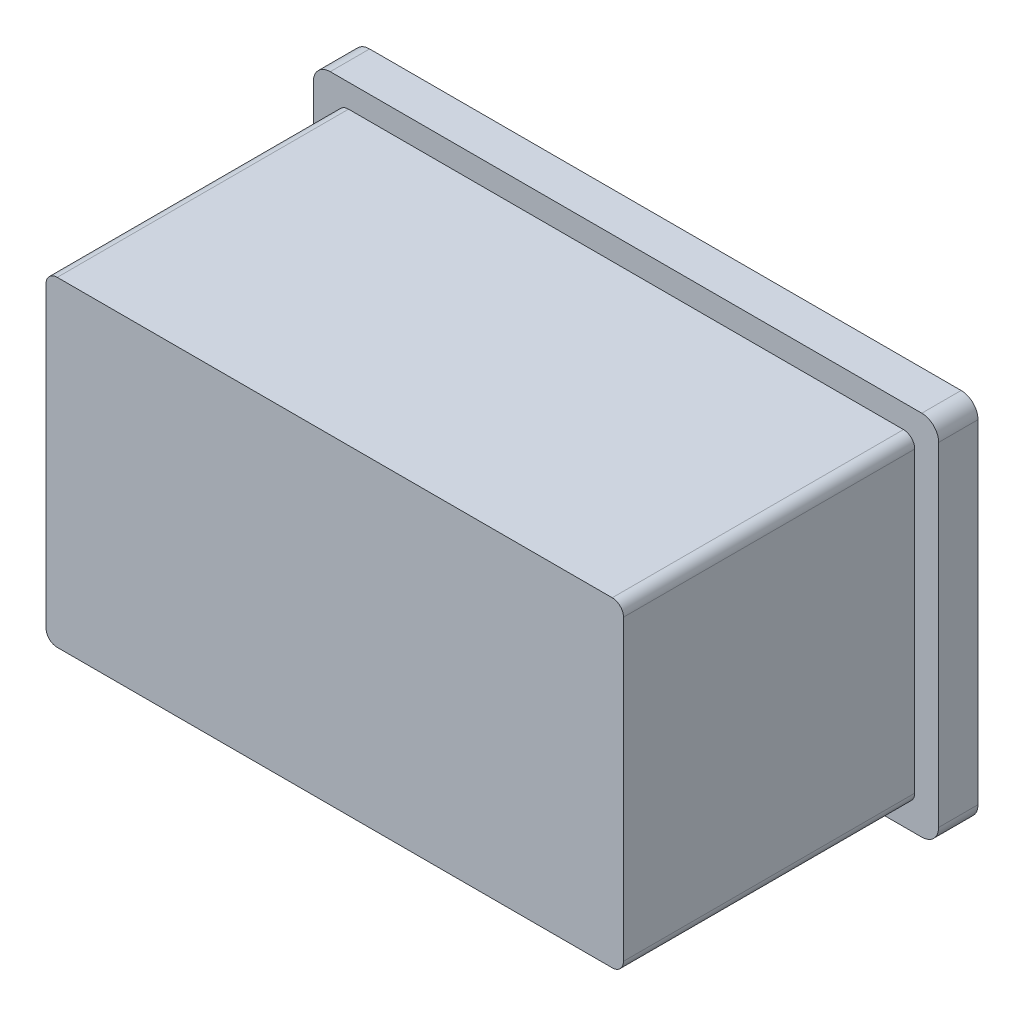
SolidWorks part; units mm, degrees
ref_plane "前视基准面" through (0, 0, 0) normal (0, 0, 1) x (1, 0, 0)
ref_plane "上视基准面" through (0, 0, 0) normal (0, 1, 0) x (1, 0, 0)
ref_plane "右视基准面" through (0, 0, 0) normal (1, 0, 0) x (0, 0, -1)
other "Configuration Table"
sketch "草图1" plane through (0, 0, 0) normal (0, 0, 1) x (1, 0, 0)
  line L0 (33.5, 5) -> (133.5, 5)
  line L1 (135.5, 7) -> (135.5, 63.5)
  line L2 (133.5, 65.5) -> (33.5, 65.5)
  line L3 (31.5, 63.5) -> (31.5, 7)
  arc A0 (133.5, 5) -> (135.5, 7) centre (133.5, 7) ccw
  arc A1 (135.5, 63.5) -> (133.5, 65.5) centre (133.5, 63.5) ccw
  arc A2 (33.5, 65.5) -> (31.5, 63.5) centre (33.5, 63.5) ccw
  arc A3 (31.5, 7) -> (33.5, 5) centre (33.5, 7) ccw
extrude "Printer_body_manufacturer_envelope_not_measured" [suppressed] add sketch "草图1" along normal blind 56.8 from offset 2
sketch "草图2" plane through (0, 0, 0) normal (0, 0, 1) x (1, 0, 0)
  line L0 (30.9, 4) -> (136.1, 4)
  line L1 (139.1, 7) -> (139.1, 66.3)
  line L2 (136.1, 69.3) -> (30.9, 69.3)
  line L3 (27.9, 66.3) -> (27.9, 7)
  arc A0 (136.1, 4) -> (139.1, 7) centre (136.1, 7) ccw
  arc A1 (139.1, 66.3) -> (136.1, 69.3) centre (136.1, 66.3) ccw
  arc A2 (30.9, 69.3) -> (27.9, 66.3) centre (30.9, 66.3) ccw
  arc A3 (27.9, 7) -> (30.9, 4) centre (30.9, 7) ccw
extrude "Original_printer_front_flange" [suppressed] add sketch "草图2" along normal blind 2 from offset 0
sketch "草图3" plane through (0, 0, 0) normal (0, 0, 1) x (1, 0, 0)
  line L1 (45, 4) -> (55, 4)
  line L2 (45, 4) -> (45, 5)
  line L3 (45, 5) -> (55, 5)
  line L4 (55, 4) -> (55, 5)
extrude "Printer_floor_contact_foot_1" [suppressed] add sketch "草图3" along normal blind 35 from offset 8
sketch "草图4" plane through (0, 0, 0) normal (0, 0, 1) x (1, 0, 0)
  line L1 (110, 4) -> (120, 4)
  line L2 (110, 4) -> (110, 5)
  line L3 (110, 5) -> (120, 5)
  line L4 (120, 4) -> (120, 5)
extrude "Printer_floor_contact_foot_2" [suppressed] add sketch "草图4" along normal blind 35 from offset 8
sketch "草图5" plane through (0, 0, 0) normal (0, 0, 1) x (1, 0, 0)
  line L0 (34.15, 8.15) -> (132.85, 8.15)
  line L1 (134.85, 10.15) -> (134.85, 63.15)
  line L2 (132.85, 65.15) -> (34.15, 65.15)
  line L3 (32.15, 63.15) -> (32.15, 10.15)
  arc A0 (132.85, 8.15) -> (134.85, 10.15) centre (132.85, 10.15) ccw
  arc A1 (134.85, 63.15) -> (132.85, 65.15) centre (132.85, 63.15) ccw
  arc A2 (34.15, 65.15) -> (32.15, 63.15) centre (34.15, 63.15) ccw
  arc A3 (32.15, 10.15) -> (34.15, 8.15) centre (34.15, 10.15) ccw
extrude "V09_H_body102p7x57_from_new_manual" add sketch "草图5" along normal blind 51.8 from offset 7
sketch "草图6" plane through (0, 0, 0) normal (0, 0, 1) x (1, 0, 0)
  line L0 (30.9, 4) -> (136.1, 4)
  line L1 (139.1, 7) -> (139.1, 66.3)
  line L2 (136.1, 69.3) -> (30.9, 69.3)
  line L3 (27.9, 66.3) -> (27.9, 7)
  arc A0 (136.1, 4) -> (139.1, 7) centre (136.1, 7) ccw
  arc A1 (139.1, 66.3) -> (136.1, 69.3) centre (136.1, 66.3) ccw
  arc A2 (30.9, 69.3) -> (27.9, 66.3) centre (30.9, 66.3) ccw
  arc A3 (27.9, 7) -> (30.9, 4) centre (30.9, 7) ccw
extrude "V09_H_flange111p2x65p3_depth7" add sketch "草图6" along normal blind 7 from offset 0
